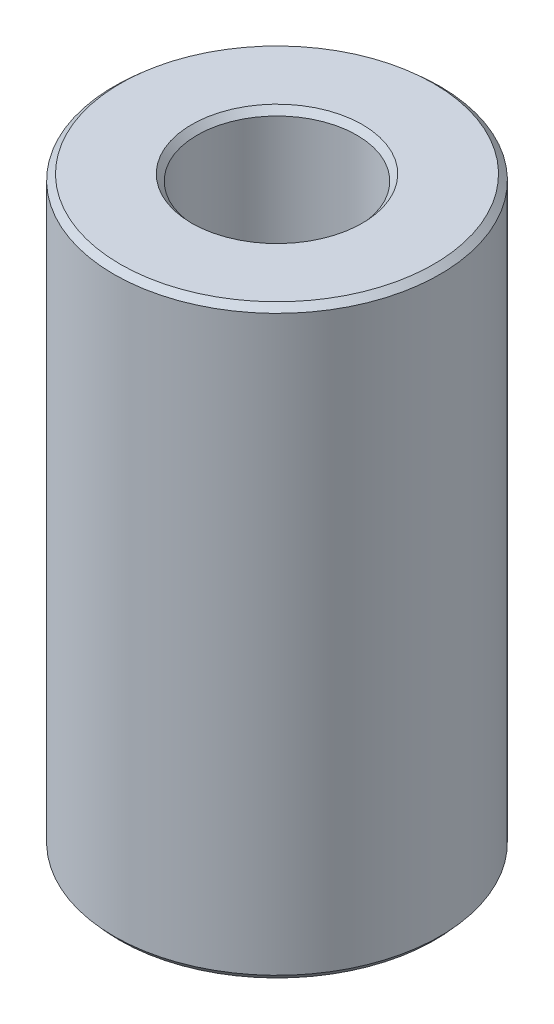
SolidWorks part; units mm, degrees
ref_plane "Front Plane" through (0, 0, 0) normal (0, 0, 1) x (1, 0, 0)
ref_plane "Top Plane" through (0, 0, 0) normal (0, 1, 0) x (1, 0, 0)
ref_plane "Right Plane" through (0, 0, 0) normal (1, 0, 0) x (0, 0, -1)
sketch "Sketch1" plane through (0, 0, 0) normal (0, 1, 0) x (1, 0, 0)
  circle A0 centre (0, 0) radius 47.5
  dimension "SLEEVE_OD" = 95
extrude "Boss-Extrude1" add sketch "Sketch1" along normal blind 170.591
sketch "Sketch2" plane through (0, 0, 0) normal (0, 1, 0) x (1, 0, 0)
  circle A0 centre (0, 0) radius 23.2626
  dimension "BORE_D" = 46.5252
extrude "Cut-Extrude1" cut sketch "Sketch2" along normal through all
chamfer "Chamfer1" distance 1.6361 angle 48.23 4 edges at (0, 170.591, 23.2626) (0, 0, 23.2626) (0, 0, 47.5) (0, 170.591, 47.5) first distance on face at (0, 170.591, 23.2626) first distance on face at (0, 0, 23.2626) first distance on face at (0, 170.591, 47.5)
